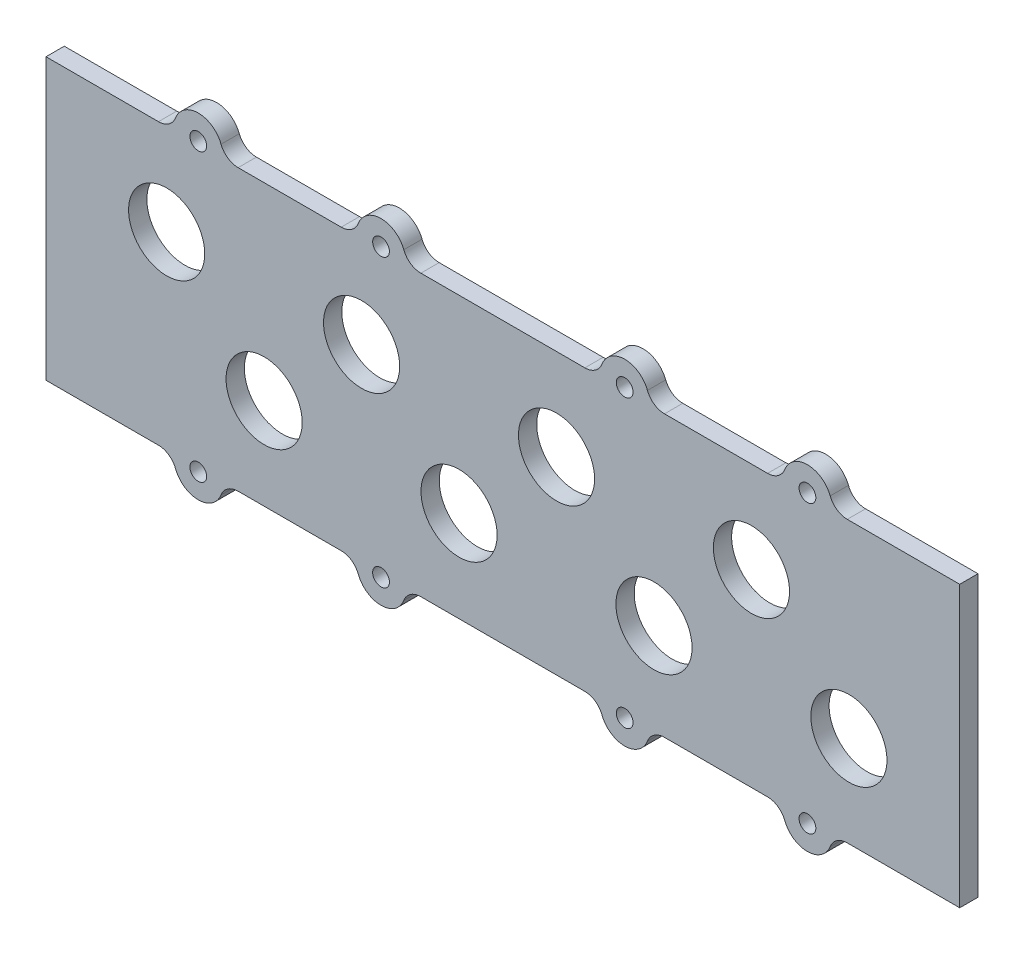
SolidWorks part; units mm, degrees
material "Aircraft Ply"
ref_plane "Front Plane" through (0, 0, 0) normal (0, 0, 1) x (1, 0, 0)
ref_plane "Top Plane" through (0, 0, 0) normal (0, 1, 0) x (1, 0, 0)
ref_plane "Right Plane" through (0, 0, 0) normal (1, 0, 0) x (0, 0, -1)
sketch "Sketch1" plane through (0, 0, 0) normal (0, 0, 1) x (1, 0, 0)
  line L0 (-75, 8) -> (75, 8) construction
  line L1 (-75, 0) -> (75, 0) construction
  line L8 (-75, 23) -> (-75, -23)
  line L9 (-43.4617, -23) -> (-26.5383, -23)
  line L10 (-13.4617, -23) -> (13.4617, -23)
  line L11 (26.5383, -23) -> (43.4617, -23)
  line L12 (75, -23) -> (75, 23)
  line L13 (43.4617, 23) -> (26.5383, 23)
  line L14 (13.4617, 23) -> (-13.4617, 23)
  line L15 (-26.5383, 23) -> (-43.4617, 23)
  line L16 (-75, 23) -> (-75, -23)
  line L17 (-43.4617, -23) -> (-26.5383, -23)
  line L18 (-13.4617, -23) -> (13.4617, -23)
  line L19 (26.5383, -23) -> (43.4617, -23)
  line L20 (75, -23) -> (75, 23)
  line L21 (43.4617, 23) -> (26.5383, 23)
  line L22 (13.4617, 23) -> (-13.4617, 23)
  line L23 (-26.5383, 23) -> (-43.4617, 23)
  line L30 (-75, -23) -> (-56.5383, -23)
  line L31 (-75, -23) -> (-56.5383, -23)
  line L32 (56.5383, -23) -> (75, -23)
  line L33 (56.5383, -23) -> (75, -23)
  line L34 (75, 23) -> (56.5383, 23)
  line L35 (75, 23) -> (56.5383, 23)
  line L36 (-56.5383, 23) -> (-75, 23)
  line L37 (-56.5383, 23) -> (-75, 23)
  circle A0 centre (-50, 23.5) radius 1.375 construction
  circle A1 centre (-20, 23.5) radius 1.375 construction
  circle A2 centre (20, 23.5) radius 1.375 construction
  circle A3 centre (50, 23.5) radius 1.375 construction
  circle A4 centre (50, -23.5) radius 1.375 construction
  circle A5 centre (20, -23.5) radius 1.375 construction
  circle A6 centre (-20, -23.5) radius 1.375 construction
  circle A7 centre (-50, -23.5) radius 1.375 construction
  circle A8 centre (-50, -23.5) radius 1.375
  circle A9 centre (-20, -23.5) radius 1.375
  circle A10 centre (20, -23.5) radius 1.375
  circle A11 centre (50, -23.5) radius 1.375
  circle A12 centre (50, 23.5) radius 1.375
  circle A13 centre (20, 23.5) radius 1.375
  circle A14 centre (-20, 23.5) radius 1.375
  circle A15 centre (-50, 23.5) radius 1.375
  circle A16 centre (-55.1927, 8) radius 6.25
  circle A17 centre (-23.1927, 8) radius 6.25
  circle A18 centre (8.8073, 8) radius 6.25
  circle A19 centre (40.8073, 8) radius 6.25
  circle A20 centre (-39.1927, -8) radius 6.25
  circle A21 centre (-7.1927, -8) radius 6.25
  circle A22 centre (24.8073, -8) radius 6.25
  circle A23 centre (56.8073, -8) radius 6.25
  arc A29 (-53.7362, -24.9286) -> (-56.5383, -23) centre (-56.5383, -26) ccw
  arc A30 (-53.7362, -24.9286) -> (-46.2638, -24.9286) centre (-50, -23.5) ccw
  arc A31 (-43.4617, -23) -> (-46.2638, -24.9286) centre (-43.4617, -26) ccw
  arc A32 (-23.7362, -24.9286) -> (-26.5383, -23) centre (-26.5383, -26) ccw
  arc A33 (-23.7362, -24.9286) -> (-16.2638, -24.9286) centre (-20, -23.5) ccw
  arc A34 (-13.4617, -23) -> (-16.2638, -24.9286) centre (-13.4617, -26) ccw
  arc A35 (16.2638, -24.9286) -> (13.4617, -23) centre (13.4617, -26) ccw
  arc A36 (16.2638, -24.9286) -> (23.7362, -24.9286) centre (20, -23.5) ccw
  arc A37 (26.5383, -23) -> (23.7362, -24.9286) centre (26.5383, -26) ccw
  arc A38 (46.2638, -24.9286) -> (43.4617, -23) centre (43.4617, -26) ccw
  arc A39 (46.2638, -24.9286) -> (53.7362, -24.9286) centre (50, -23.5) ccw
  arc A40 (56.5383, -23) -> (53.7362, -24.9286) centre (56.5383, -26) ccw
  arc A43 (53.7362, 24.9286) -> (56.5383, 23) centre (56.5383, 26) ccw
  arc A44 (53.7362, 24.9286) -> (46.2638, 24.9286) centre (50, 23.5) ccw
  arc A45 (43.4617, 23) -> (46.2638, 24.9286) centre (43.4617, 26) ccw
  arc A46 (23.7362, 24.9286) -> (26.5383, 23) centre (26.5383, 26) ccw
  arc A47 (23.7362, 24.9286) -> (16.2638, 24.9286) centre (20, 23.5) ccw
  arc A48 (13.4617, 23) -> (16.2638, 24.9286) centre (13.4617, 26) ccw
  arc A49 (-16.2638, 24.9286) -> (-13.4617, 23) centre (-13.4617, 26) ccw
  arc A50 (-16.2638, 24.9286) -> (-23.7362, 24.9286) centre (-20, 23.5) ccw
  arc A51 (-26.5383, 23) -> (-23.7362, 24.9286) centre (-26.5383, 26) ccw
  arc A52 (-46.2638, 24.9286) -> (-43.4617, 23) centre (-43.4617, 26) ccw
  arc A53 (-46.2638, 24.9286) -> (-53.7362, 24.9286) centre (-50, 23.5) ccw
  arc A54 (-56.5383, 23) -> (-53.7362, 24.9286) centre (-56.5383, 26) ccw
  arc A57 (-53.7362, -24.9286) -> (-56.5383, -23) centre (-56.5383, -26) ccw
  arc A58 (-53.7362, -24.9286) -> (-46.2638, -24.9286) centre (-50, -23.5) ccw
  arc A59 (-43.4617, -23) -> (-46.2638, -24.9286) centre (-43.4617, -26) ccw
  arc A60 (-23.7362, -24.9286) -> (-26.5383, -23) centre (-26.5383, -26) ccw
  arc A61 (-23.7362, -24.9286) -> (-16.2638, -24.9286) centre (-20, -23.5) ccw
  arc A62 (-13.4617, -23) -> (-16.2638, -24.9286) centre (-13.4617, -26) ccw
  arc A63 (16.2638, -24.9286) -> (13.4617, -23) centre (13.4617, -26) ccw
  arc A64 (16.2638, -24.9286) -> (23.7362, -24.9286) centre (20, -23.5) ccw
  arc A65 (26.5383, -23) -> (23.7362, -24.9286) centre (26.5383, -26) ccw
  arc A66 (46.2638, -24.9286) -> (43.4617, -23) centre (43.4617, -26) ccw
  arc A67 (46.2638, -24.9286) -> (53.7362, -24.9286) centre (50, -23.5) ccw
  arc A68 (56.5383, -23) -> (53.7362, -24.9286) centre (56.5383, -26) ccw
  arc A71 (53.7362, 24.9286) -> (56.5383, 23) centre (56.5383, 26) ccw
  arc A72 (53.7362, 24.9286) -> (46.2638, 24.9286) centre (50, 23.5) ccw
  arc A73 (43.4617, 23) -> (46.2638, 24.9286) centre (43.4617, 26) ccw
  arc A74 (23.7362, 24.9286) -> (26.5383, 23) centre (26.5383, 26) ccw
  arc A75 (23.7362, 24.9286) -> (16.2638, 24.9286) centre (20, 23.5) ccw
  arc A76 (13.4617, 23) -> (16.2638, 24.9286) centre (13.4617, 26) ccw
  arc A77 (-16.2638, 24.9286) -> (-13.4617, 23) centre (-13.4617, 26) ccw
  arc A78 (-16.2638, 24.9286) -> (-23.7362, 24.9286) centre (-20, 23.5) ccw
  arc A79 (-26.5383, 23) -> (-23.7362, 24.9286) centre (-26.5383, 26) ccw
  arc A80 (-46.2638, 24.9286) -> (-43.4617, 23) centre (-43.4617, 26) ccw
  arc A81 (-46.2638, 24.9286) -> (-53.7362, 24.9286) centre (-50, 23.5) ccw
  arc A82 (-56.5383, 23) -> (-53.7362, 24.9286) centre (-56.5383, 26) ccw
  dimension "D2" = 12.5
  dimension "D3" = 8
  dimension "D1" = 0
  dimension "D4" = 4
  dimension "D5" = 2
extrude "Boss-Extrude1" add sketch "Sketch1" along normal blind 3
sketch "Sketch2" plane through (0, 0, 3) normal (0, 0, 1) x (1, 0, 0)
  line L0 (-55.1927, 8) -> (-39.1927, -8) construction
  line L1 (-48.449, 14.7437) -> (-32.449, -1.2563)
  line L2 (-61.9364, 1.2563) -> (-45.9364, -14.7437)
  line L3 (-23.1927, 8) -> (-7.1927, -8) construction
  line L4 (-16.449, 14.7437) -> (-0.449, -1.2563)
  line L5 (-29.9364, 1.2563) -> (-13.9364, -14.7437)
  line L6 (24.8073, -8) -> (8.8073, 8) construction
  line L7 (18.0636, -14.7437) -> (2.0636, 1.2563)
  line L8 (31.551, -1.2563) -> (15.551, 14.7437)
  line L9 (40.8073, 8) -> (56.8073, -8) construction
  line L10 (47.551, 14.7437) -> (63.551, -1.2563)
  line L11 (34.0636, 1.2563) -> (50.0636, -14.7437)
  arc A10 (-48.449, 14.7437) -> (-61.9364, 1.2563) centre (-55.1927, 8) ccw
  arc A11 (-45.9364, -14.7437) -> (-32.449, -1.2563) centre (-39.1927, -8) ccw
  arc A12 (-16.449, 14.7437) -> (-29.9364, 1.2563) centre (-23.1927, 8) ccw
  arc A13 (-13.9364, -14.7437) -> (-0.449, -1.2563) centre (-7.1927, -8) ccw
  arc A14 (18.0636, -14.7437) -> (31.551, -1.2563) centre (24.8073, -8) ccw
  arc A15 (15.551, 14.7437) -> (2.0636, 1.2563) centre (8.8073, 8) ccw
  arc A16 (47.551, 14.7437) -> (34.0636, 1.2563) centre (40.8073, 8) ccw
  arc A17 (50.0636, -14.7437) -> (63.551, -1.2563) centre (56.8073, -8) ccw
  text T0 "      1" font "Century Gothic" height in points 18
  point P2 (-47.1927, 0)
  point P7 (-15.1927, 0)
  point P14 (16.8073, 0)
  point P21 (48.8073, 0)
